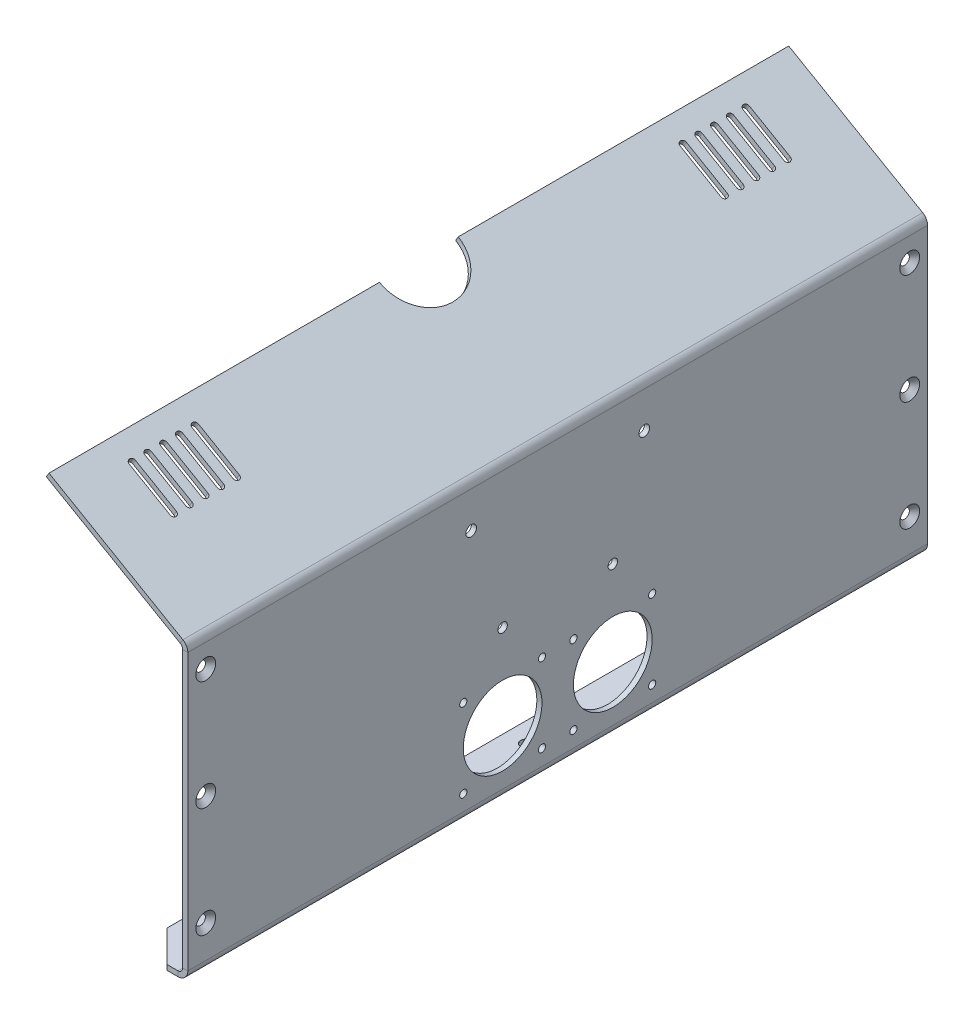
SolidWorks part; units mm, degrees
note: The reader was unsure of these and kept them because the rebuilt part matched: bend radius of "BaseBend1", "BaseBend2".
material "5052-H32"
ref_plane "Front Plane" through (0, 0, 0) normal (0, 0, 1) x (1, 0, 0)
ref_plane "Top Plane" through (0, 0, 0) normal (0, 1, 0) x (1, 0, 0)
ref_plane "Right Plane" through (0, 0, 0) normal (1, 0, 0) x (0, 0, -1)
sketch "Sketch1" plane through (0, 0, 0) normal (0, 0, 1) x (1, 0, 0)
  line L0 (-30, 0) -> (0, 0)
  line L1 (0, 0) -> (0, 180)
  line L2 (0, 180) -> (-86.6025, 230)
  dimension "D1" = 30
  dimension "D2" = 180
  dimension "D3" = 120
  dimension "D4" = 100
base flange "Base-Flange1" sketch "Sketch1" end condition mid plane depth 470 reverse direction no thickness 3.26 reverse thickness direction no bend radius 3.048
bend "BaseBend1" bend radius 3.048 bend angle 90 parameters "D5"=1
bend "BaseBend2" bend radius 3.048 bend angle 60 parameters "D5"=3
sketch "Sketch6" plane through (0, 0, 0) normal (0, 1, 0) x (1, 0, 0)
  line L1 (-17.387, 0.5952) -> (-17.387, -199.4048) construction
  line L2 (-17.387, 0.5952) -> (-17.387, 200.5952) construction
  circle A0 centre (-17.387, 0.5952) radius 3.5
  circle A1 centre (-17.387, -199.4048) radius 3.5
  circle A2 centre (-17.387, -99.4048) radius 3.5
  circle A3 centre (-17.387, 200.5952) radius 3.5
  circle A4 centre (-17.387, 100.5952) radius 3.5
  dimension "D2" = 7
  dimension "D1" = 200
extrude "Cut-Extrude1" cut sketch "Sketch6" against normal blind 10 normal cut yes
sketch "Sketch7" plane through (0, 0, 0) normal (0, 1, 0) x (1, 0, 0)
  line L0 (0, 0) -> (-80.6782, 0) construction
  line L1 (-30, -114.4048) -> (-3.048, -141.3568)
  line L2 (-30, -235) -> (-30, 235) construction
  line L3 (-3.048, -141.3568) -> (-3.048, -157.4528)
  line L4 (-3.048, -157.4528) -> (-30, -184.4048)
  line L5 (-30, -184.4048) -> (-30, -114.4048)
  line L6 (-3.048, -235) -> (-3.048, 235) construction
  line L7 (-30, 184.4048) -> (-30, 114.4048)
  line L8 (-3.048, 157.4528) -> (-30, 184.4048)
  line L9 (-3.048, 141.3568) -> (-3.048, 157.4528)
  line L10 (-30, 114.4048) -> (-3.048, 141.3568)
  circle A0 centre (-17.387, -99.4048) radius 3.5 construction
  circle A1 centre (-17.387, -199.4048) radius 3.5 construction
  dimension "D1" = 15
  dimension "D2" = 15
extrude "Cut-Extrude2" [suppressed] cut sketch "Sketch7" against normal up to surface (3.175 mm away)
chamfer "Chamfer1" distance 20 angle 45 2 edges at (-30, -1.63, 235) (-30, -1.63, -235)
sketch "Sketch8" plane through (3.26, 0, 0) normal (1, 0, 0) x (0, 0, -1)
  line L0 (0, 0) -> (0, 178.2402) construction
  line L1 (-235, 178.2402) -> (235, 178.2402) construction
  circle A2 centre (-223.6192, 163.426) radius 3
  circle A3 centre (-223.6192, 93.576) radius 3
  circle A4 centre (-223.6192, 23.726) radius 3
  circle A5 centre (223.6192, 23.726) radius 3
  circle A6 centre (223.6192, 93.576) radius 3
  circle A7 centre (223.6192, 163.426) radius 3
  dimension "D1" = 6
extrude "Cut-Extrude3" cut sketch "Sketch8" against normal up to surface (3.26 mm away) normal cut yes up to face at (0, 90.6441, 0)
sketch "Sketch10" [suppressed] plane through (0, -3.175, 0) normal (0, -1, 0) x (-1, 0, 0)
  line L0 (3.048, -163.048) -> (25, -185) construction
  line L1 (14.024, -125.976) -> (-3.175, -125.976)
  line L2 (14.024, -125.976) -> (14.024, -174.024)
  line L3 (14.024, -174.024) -> (-3.175, -174.024)
  line L4 (-3.175, -125.976) -> (-3.175, -174.024)
  line L5 (25, -115) -> (3.048, -136.952) construction
  line L6 (-3.175, -235) -> (-3.175, 235) construction
  line L7 (0, 0) -> (25, 0) construction
  line L8 (25, -115) -> (25, 115) construction
  line L9 (-3.175, 125.976) -> (-3.175, 174.024)
  line L10 (14.024, 174.024) -> (-3.175, 174.024)
  line L11 (14.024, 125.976) -> (14.024, 174.024)
  line L12 (14.024, 125.976) -> (-3.175, 125.976)
extrude "Cut-Extrude4" [suppressed] cut sketch "Sketch10" against normal blind 15
sketch "Sketch11" plane through (3.26, 0, 0) normal (1, 0, 0) x (0, 0, -1)
  line L0 (0, 3.048) -> (0, 178.2402) construction
  line L1 (-235, 3.048) -> (235, 3.048) construction
  line L2 (-235, 178.2402) -> (235, 178.2402) construction
  line L3 (10, 13.048) -> (60, 63.048) construction
  line L4 (-10, 63.048) -> (-60, 63.048) construction
  line L5 (-10, 63.048) -> (-10, 13.048) construction
  line L6 (-10, 13.048) -> (-60, 13.048) construction
  line L7 (-60, 63.048) -> (-60, 13.048) construction
  line L8 (-10, 63.048) -> (-60, 13.048) construction
  line L9 (-10, 13.048) -> (-60, 63.048) construction
  line L10 (10, 63.048) -> (60, 13.048) construction
  line L11 (60, 63.048) -> (60, 13.048) construction
  line L12 (10, 13.048) -> (60, 13.048) construction
  line L13 (10, 63.048) -> (10, 13.048) construction
  line L14 (10, 63.048) -> (60, 63.048) construction
  circle A0 centre (-60, 63.048) radius 2.286
  circle A1 centre (-10, 63.048) radius 2.286
  circle A2 centre (-10, 13.048) radius 2.286
  circle A3 centre (-60, 13.048) radius 2.286
  circle A4 centre (-35, 38.048) radius 25
  circle A5 centre (35, 38.048) radius 25
  circle A6 centre (60, 13.048) radius 2.286
  circle A7 centre (10, 13.048) radius 2.286
  circle A8 centre (10, 63.048) radius 2.286
  circle A9 centre (60, 63.048) radius 2.286
  point P6 (-35, 38.048)
  dimension "D1" = 4.572
  dimension "D2" = 35
  dimension "D3" = 35
  dimension "D4" = 50
extrude "Cut-Extrude5" cut sketch "Sketch11" against normal up to surface (3.26 mm away) normal cut yes up to face at (0, 163.426, -220.6192)
sketch "Sketch12" plane through (0, 0, 0) normal (-1, 0, 0) x (0, 0, 1)
  circle A0 centre (35, 91.949) radius 3
  circle A1 centre (-35, 91.949) radius 3
  dimension "D1" = 6
extrude "Cut-Extrude6" cut sketch "Sketch12" against normal blind 10 normal cut yes
sketch "Sketch13" plane through (79.5723, 137.8232, 0) normal (0.5, 0.866, 0) x (0.866, -0.5, 0)
  line L0 (-175, 195) -> (-145, 195) construction
  line L1 (-175, 197) -> (-145, 197)
  line L2 (-175, 193) -> (-145, 193)
  line L3 (-91.7598, 235) -> (-190, 235) construction
  line L4 (-190, -235) -> (-190, 235) construction
  line L5 (-91.7598, 0) -> (-190, 0) construction
  line L6 (-91.7598, -235) -> (-91.7598, 235) construction
  line L7 (-175, 185) -> (-145, 185) construction
  line L8 (-175, 187) -> (-145, 187)
  line L9 (-175, 183) -> (-145, 183)
  line L10 (-175, 175) -> (-145, 175) construction
  line L11 (-175, 177) -> (-145, 177)
  line L12 (-175, 173) -> (-145, 173)
  line L13 (-175, 165) -> (-145, 165) construction
  line L14 (-175, 167) -> (-145, 167)
  line L15 (-175, 163) -> (-145, 163)
  line L16 (-175, 155) -> (-145, 155) construction
  line L17 (-175, 157) -> (-145, 157)
  line L18 (-175, 153) -> (-145, 153)
  line L19 (-175, 195) -> (-175, 185) construction
  line L20 (-175, -195) -> (-145, -195) construction
  line L21 (-175, -197) -> (-145, -197)
  line L22 (-175, -193) -> (-145, -193)
  line L23 (-175, -185) -> (-145, -185) construction
  line L24 (-175, -187) -> (-145, -187)
  line L25 (-175, -183) -> (-145, -183)
  line L26 (-175, -175) -> (-145, -175) construction
  line L27 (-175, -177) -> (-145, -177)
  line L28 (-175, -173) -> (-145, -173)
  line L29 (-175, -165) -> (-145, -165) construction
  line L30 (-175, -167) -> (-145, -167)
  line L31 (-175, -163) -> (-145, -163)
  line L32 (-175, -155) -> (-145, -155) construction
  line L33 (-175, -157) -> (-145, -157)
  line L34 (-175, -153) -> (-145, -153)
  arc A0 (-175, 197) -> (-175, 193) centre (-175, 195) ccw
  arc A1 (-145, 193) -> (-145, 197) centre (-145, 195) ccw
  arc A2 (-175, 187) -> (-175, 183) centre (-175, 185) ccw
  arc A3 (-145, 183) -> (-145, 187) centre (-145, 185) ccw
  arc A4 (-175, 177) -> (-175, 173) centre (-175, 175) ccw
  arc A5 (-145, 173) -> (-145, 177) centre (-145, 175) ccw
  arc A6 (-175, 167) -> (-175, 163) centre (-175, 165) ccw
  arc A7 (-145, 163) -> (-145, 167) centre (-145, 165) ccw
  arc A8 (-175, 157) -> (-175, 153) centre (-175, 155) ccw
  arc A9 (-145, 153) -> (-145, 157) centre (-145, 155) ccw
  arc A10 (-175, -197) -> (-175, -193) centre (-175, -195) cw
  arc A11 (-145, -193) -> (-145, -197) centre (-145, -195) cw
  arc A12 (-175, -187) -> (-175, -183) centre (-175, -185) cw
  arc A13 (-145, -183) -> (-145, -187) centre (-145, -185) cw
  arc A14 (-175, -177) -> (-175, -173) centre (-175, -175) cw
  arc A15 (-145, -173) -> (-145, -177) centre (-145, -175) cw
  arc A16 (-175, -167) -> (-175, -163) centre (-175, -165) cw
  arc A17 (-145, -163) -> (-145, -167) centre (-145, -165) cw
  arc A18 (-175, -157) -> (-175, -153) centre (-175, -155) cw
  arc A19 (-145, -153) -> (-145, -157) centre (-145, -155) cw
  point P2 (-160, 195)
  point P18 (-160, 185)
  point P25 (-160, 175)
  point P32 (-160, 165)
  point P39 (-160, 155)
  point P47 (-160, -195)
  point P54 (-160, -185)
  point P61 (-160, -175)
  point P68 (-160, -165)
  point P75 (-160, -155)
  dimension "D1" = 2
  dimension "D2" = 40
  dimension "D3" = 30
  dimension "D4" = 30
  dimension "D6" = 10
  dimension "D5" = 5
extrude "Cut-Extrude7" cut sketch "Sketch13" against normal blind 10
sketch "Sketch14" plane through (79.5723, 137.8232, 0) normal (0.5, 0.866, 0) x (0.866, -0.5, 0)
  line L0 (-190, -235) -> (-190, 235) construction
  line L1 (-190, 25) -> (-190, -25)
  arc A0 (-190, -25) -> (-190, 25) centre (-190, 0) ccw
  dimension "D1" = 50
extrude "Cut-Extrude8" cut sketch "Sketch14" against normal blind 10 normal cut yes
chamfer "Chamfer2" distance 3.3 angle 45 6 edges at (3.26, 163.426, -220.6192) (3.26, 93.576, -220.6192) (3.26, 23.726, -220.6192) (3.26, 23.726, 220.6192) (3.26, 93.576, 220.6192) (3.26, 163.426, 220.6192)
sketch "Sketch15" plane through (3.26, 0, 0) normal (1, 0, 0) x (0, 0, -1)
  line L0 (-55, 155.2402) -> (55, 155.2402) construction
  line L1 (-235, 178.2402) -> (235, 178.2402) construction
  circle A0 centre (-55, 155.2402) radius 3.375
  circle A1 centre (55, 155.2402) radius 3.375
  point P4 (0, 155.2402)
  point P5 (0, 178.2402)
  dimension "D1" = 6.75
  dimension "D2" = 110
  dimension "D3" = 23
extrude "Cut-Extrude9" cut sketch "Sketch15" against normal blind 10 normal cut yes
sketch "Bend-Lines1" [suppressed] plane through (0, 0, 0) normal (0, 1, 0) x (1, 0, 0)
sketch "Bounding-Box1" [suppressed] plane through (0, 0, 0) normal (0, 1, 0) x (1, 0, 0)
sheet metal parameters "Sheet-Metal1" thickness 3.26 parameters "D1"=2.54
flat pattern "Flat-Pattern1" [suppressed]
sketch "Bend-Lines2" plane through (0, 0, 0) normal (-1, 0, 0) x (0, 0, 1)
  line L0 (235, -0.2) -> (-235, -0.2) construction
  line L1 (235, -0.2) -> (-235, -0.2) construction
sketch3d "Bounding-Box2" [suppressed]
  line L0 (-470, -25.4, 0) -> (0, -25.4, 0) construction
  line L1 (-470, 120, 0) -> (0, 120, 0) construction
  line L2 (-470, -25.4, 0) -> (-470, 120, 0) construction
  line L3 (0, -25.4, 0) -> (0, 120, 0) construction
bend of the flat pattern "Flatten-<BaseBend1>1"
bend of the flat pattern "Flatten-<BaseBend2>1"
sheet metal parameters "Sheet-Metal2" thickness 3.26 parameters "D1"=2.54
flat pattern "Flat-Pattern1" [suppressed]
sketch "Bend-Lines2" plane through (0, 0, 0) normal (-1, 0, 0) x (0, 0, 1)
  line L0 (235, -0.2) -> (-235, -0.2) construction
  line L1 (235, -0.2) -> (-235, -0.2) construction
sketch3d "Bounding-Box2" [suppressed]
  line L0 (-470, -25.4, 0) -> (0, -25.4, 0) construction
  line L1 (-470, 120, 0) -> (0, 120, 0) construction
  line L2 (-470, -25.4, 0) -> (-470, 120, 0) construction
  line L3 (0, -25.4, 0) -> (0, 120, 0) construction
bend of the flat pattern "Flatten-<BaseBend1>1"
bend of the flat pattern "Flatten-<BaseBend2>2"
sheet metal parameters "Sheet-Metal3" thickness 3.26 parameters "D1"=2.54
flat pattern "Flat-Pattern1" [suppressed]
sketch "Bend-Lines2" plane through (0, 0, 0) normal (-1, 0, 0) x (0, 0, 1)
  line L0 (235, -0.2) -> (-235, -0.2) construction
  line L1 (235, -0.2) -> (-235, -0.2) construction
sketch3d "Bounding-Box2" [suppressed]
  line L0 (-470, -25.4, 0) -> (0, -25.4, 0) construction
  line L1 (-470, 120, 0) -> (0, 120, 0) construction
  line L2 (-470, -25.4, 0) -> (-470, 120, 0) construction
  line L3 (0, -25.4, 0) -> (0, 120, 0) construction
bend of the flat pattern "Flatten-<BaseBend1>1"
bend of the flat pattern "Flatten-<BaseBend2>3"
sheet metal parameters "Sheet-Metal4" thickness 3.26 parameters "D1"=2.54
flat pattern "Flat-Pattern1"
sketch "Bend-Lines2" plane through (0, 0, 0) normal (-1, 0, 0) x (0, 0, 1)
  line L0 (235, -0.8176) -> (-235, -0.8176) construction
  line L1 (235, -0.8176) -> (-235, -0.8176) construction
  line L2 (-235, 181.7737) -> (235, 181.7737) construction
  line L3 (-235, 181.7737) -> (235, 181.7737) construction
sketch3d "Bounding-Box2" [suppressed]
  line L0 (-470, -26.6352, 0) -> (0, -26.6352, 0) construction
  line L1 (-470, 282.4974, 0) -> (0, 282.4974, 0) construction
  line L2 (-470, -26.6352, 0) -> (-470, 282.4974, 0) construction
  line L3 (0, -26.6352, 0) -> (0, 282.4974, 0) construction
bend of the flat pattern "Flatten-<BaseBend1>1"
bend of the flat pattern "Flatten-<BaseBend2>4"
sheet metal parameters "Sheet-Metal6" thickness 3.26 parameters "D1"=2.54
flat pattern "Flat-Pattern1"
sketch "Bend-Lines2" plane through (0, 0, 0) normal (-1, 0, 0) x (0, 0, 1)
  line L0 (235, -0.8176) -> (-235, -0.8176) construction
  line L1 (235, -0.8176) -> (-235, -0.8176) construction
  line L2 (-235, 181.7737) -> (235, 181.7737) construction
  line L3 (-235, 181.7737) -> (235, 181.7737) construction
sketch3d "Bounding-Box2" [suppressed]
  line L0 (-470, -26.6352, 0) -> (0, -26.6352, 0) construction
  line L1 (-470, 282.4974, 0) -> (0, 282.4974, 0) construction
  line L2 (-470, -26.6352, 0) -> (-470, 282.4974, 0) construction
  line L3 (0, -26.6352, 0) -> (0, 282.4974, 0) construction
bend of the flat pattern "Flatten-<BaseBend1>1"
bend of the flat pattern "Flatten-<BaseBend2>4"
sheet metal parameters "Sheet-Metal8" thickness 3.26 parameters "D1"=2.54
flat pattern "Flat-Pattern1"
sketch "Bend-Lines2" plane through (0, 0, 0) normal (-1, 0, 0) x (0, 0, 1)
  line L0 (235, -0.5927) -> (-235, -0.5927) construction
  line L1 (235, -0.5927) -> (-235, -0.5927) construction
  line L2 (-235, 180.6674) -> (235, 180.6674) construction
  line L3 (-235, 180.6674) -> (235, 180.6674) construction
sketch3d "Bounding-Box2" [suppressed]
  line L0 (-470, -31.1854, 0) -> (0, -31.1854, 0) construction
  line L1 (-470, 281.3348, 0) -> (0, 281.3348, 0) construction
  line L2 (-470, -31.1854, 0) -> (-470, 281.3348, 0) construction
  line L3 (0, -31.1854, 0) -> (0, 281.3348, 0) construction
bend of the flat pattern "Flatten-<BaseBend1>1"
bend of the flat pattern "Flatten-<BaseBend2>4"
sheet metal parameters "Sheet-Metal19" thickness 3.26 parameters "D1"=2.54
flat pattern "Flat-Pattern1"
sketch "Bend-Lines2" plane through (0, 0, 0) normal (-1, 0, 0) x (0, 0, 1)
  line L0 (235, -0.5927) -> (-235, -0.5927) construction
  line L1 (235, -0.5927) -> (-235, -0.5927) construction
  line L2 (-235, 180.6674) -> (235, 180.6674) construction
  line L3 (-235, 180.6674) -> (235, 180.6674) construction
sketch3d "Bounding-Box2" [suppressed]
  line L0 (-470, -31.1854, 0) -> (0, -31.1854, 0) construction
  line L1 (-470, 281.3348, 0) -> (0, 281.3348, 0) construction
  line L2 (-470, -31.1854, 0) -> (-470, 281.3348, 0) construction
  line L3 (0, -31.1854, 0) -> (0, 281.3348, 0) construction
bend of the flat pattern "Flatten-<BaseBend1>1"
bend of the flat pattern "Flatten-<BaseBend2>4"
sheet metal parameters "Sheet-Metal20" thickness 3.26 parameters "D1"=2.54
flat pattern "Flat-Pattern1"
sketch "Bend-Lines2" plane through (0, 0, 0) normal (-1, 0, 0) x (0, 0, 1)
  line L0 (235, -0.5927) -> (-235, -0.5927) construction
  line L1 (235, -0.5927) -> (-235, -0.5927) construction
  line L2 (-235, 180.6674) -> (235, 180.6674) construction
  line L3 (-235, 180.6674) -> (235, 180.6674) construction
sketch3d "Bounding-Box2" [suppressed]
  line L0 (-470, -31.1854, 0) -> (0, -31.1854, 0) construction
  line L1 (-470, 281.3348, 0) -> (0, 281.3348, 0) construction
  line L2 (-470, -31.1854, 0) -> (-470, 281.3348, 0) construction
  line L3 (0, -31.1854, 0) -> (0, 281.3348, 0) construction
bend of the flat pattern "Flatten-<BaseBend1>1"
bend of the flat pattern "Flatten-<BaseBend2>4"
sheet metal parameters "Sheet-Metal21" thickness 3.26 parameters "D1"=2.54
flat pattern "Flat-Pattern1"
sketch "Bend-Lines2" plane through (0, 0, 0) normal (-1, 0, 0) x (0, 0, 1)
  line L0 (235, -0.5927) -> (-235, -0.5927) construction
  line L1 (235, -0.5927) -> (-235, -0.5927) construction
  line L2 (-235, 180.6674) -> (235, 180.6674) construction
  line L3 (-235, 180.6674) -> (235, 180.6674) construction
sketch3d "Bounding-Box2" [suppressed]
  line L0 (-470, -31.1854, 0) -> (0, -31.1854, 0) construction
  line L1 (-470, 281.3348, 0) -> (0, 281.3348, 0) construction
  line L2 (-470, -31.1854, 0) -> (-470, 281.3348, 0) construction
  line L3 (0, -31.1854, 0) -> (0, 281.3348, 0) construction
bend of the flat pattern "Flatten-<BaseBend1>1"
bend of the flat pattern "Flatten-<BaseBend2>4"
sheet metal parameters "Sheet-Metal22" thickness 3.26 parameters "D1"=2.54
flat pattern "Flat-Pattern1"
sketch "Bend-Lines2" plane through (0, 0, 0) normal (-1, 0, 0) x (0, 0, 1)
  line L0 (235, -0.5927) -> (-235, -0.5927) construction
  line L1 (235, -0.5927) -> (-235, -0.5927) construction
  line L2 (-235, 180.6674) -> (235, 180.6674) construction
  line L3 (-235, 180.6674) -> (235, 180.6674) construction
sketch3d "Bounding-Box2" [suppressed]
  line L0 (-470, -31.1854, 0) -> (0, -31.1854, 0) construction
  line L1 (-470, 281.3348, 0) -> (0, 281.3348, 0) construction
  line L2 (-470, -31.1854, 0) -> (-470, 281.3348, 0) construction
  line L3 (0, -31.1854, 0) -> (0, 281.3348, 0) construction
bend of the flat pattern "Flatten-<BaseBend1>1"
bend of the flat pattern "Flatten-<BaseBend2>4"
